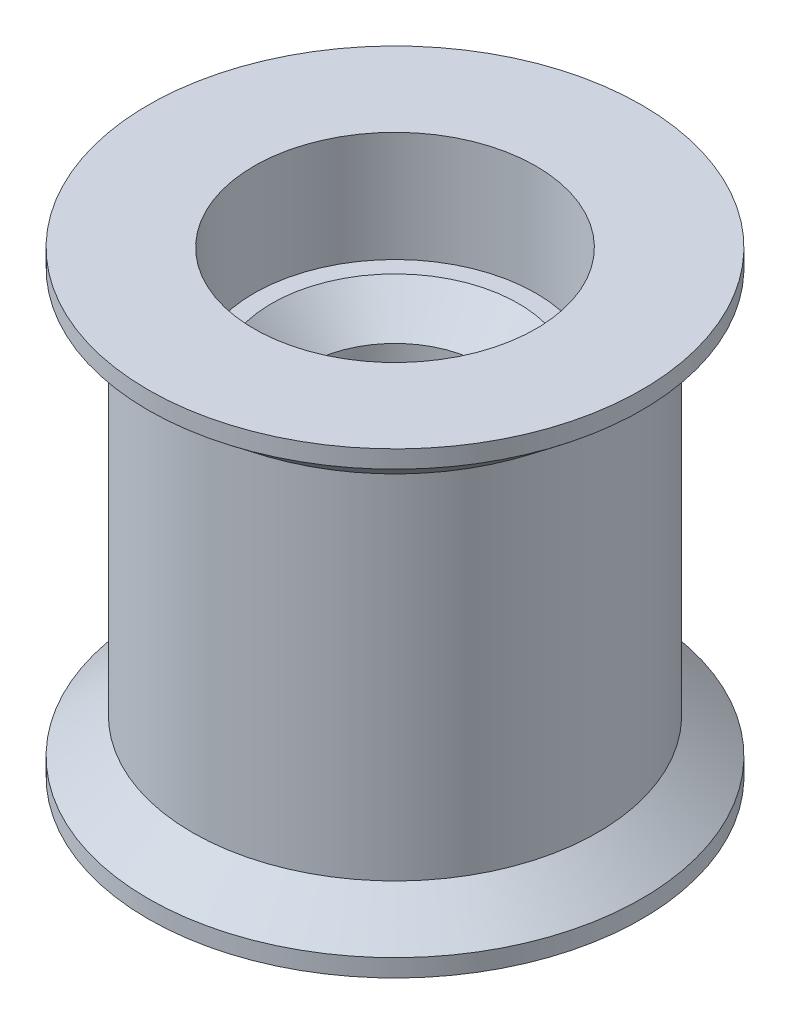
SolidWorks part; units mm, degrees
material "Markforged"
ref_plane "Front Plane" through (0, 0, 0) normal (0, 0, 1) x (1, 0, 0)
ref_plane "Top Plane" through (0, 0, 0) normal (0, 1, 0) x (1, 0, 0)
ref_plane "Right Plane" through (0, 0, 0) normal (1, 0, 0) x (0, 0, -1)
other "Bounding Box"
ref_plane "Default Plane" through (-8.9266, -12.7485, 0) normal (-0.1736, 0.9848, 0) x (0.9848, 0.1736, 0)
sketch "Sketch2" plane through (0, 0, 0) normal (1, 0, 0) x (0, 0, -1)
  line L0 (0, 0) -> (196218.8196, 0) construction
  line L1 (0, 0) -> (0, 196218.8196) construction
  line L2 (2.5, 0) -> (2.5, 3.375)
  line L3 (2.5, 3.375) -> (4, 3.375)
  line L4 (4, 3.375) -> (4, 6.5)
  line L5 (4, 6.5) -> (7, 6.5)
  line L6 (7, 6.5) -> (7, 6)
  line L7 (7, 6) -> (5.75, 5)
  line L8 (5.75, 5) -> (5.75, 0)
  line L9 (5.75, 0) -> (2.5, 0)
  dimension "D1" = 5
  dimension "D2" = 8
  dimension "D3" = 3.125
  dimension "D4" = 11.5
  dimension "D5" = 14
  dimension "D6" = 10
  dimension "D7" = 0.5
  dimension "D8" = 1.5
revolve "Revolve1" add sketch "Sketch2" angle 360 about L1
mirror "Mirror1" about plane through (0, 0, 0) normal (0, 1, 0) of "Revolve1"
chamfer "Chamfer1" distance 1 angle 45 2 edges at (0, -3.375, -2.5) (0, 3.375, -2.5)
